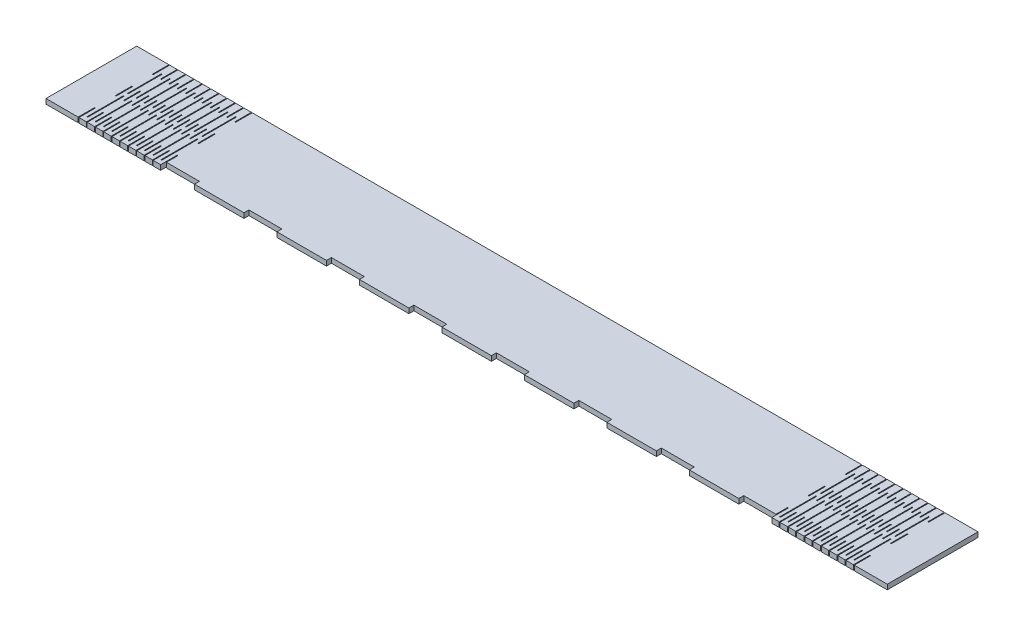
SolidWorks part; units mm, degrees
material "Beech"
ref_plane "Front Plane" through (0, 0, 0) normal (0, 0, 1) x (1, 0, 0)
ref_plane "Top Plane" through (0, 0, 0) normal (0, 1, 0) x (1, 0, 0)
ref_plane "Right Plane" through (0, 0, 0) normal (1, 0, 0) x (0, 0, -1)
sketch "Sketch1" plane through (0, 0, 0) normal (0, 1, 0) x (1, 0, 0)
  line L0 (-185, 27.5) -> (-185, -27.5)
  line L1 (-255, -27.5) -> (255, -27.5)
  line L2 (-255, -27.5) -> (-255, 27.5)
  line L3 (-255, 27.5) -> (255, 27.5)
  line L4 (255, -27.5) -> (255, 27.5)
  line L5 (-255, -27.5) -> (255, 27.5) construction
  line L6 (-255, 27.5) -> (255, -27.5) construction
  line L7 (185, 27.5) -> (185, -27.5)
  point P0 (0, 0)
  point P6 (-185, 27.5)
  point P7 (185, 27.5)
  point P10 (235, 27.5)
  point P13 (-235, 27.5)
  dimension "D1" = 510
  dimension "D2" = 70
  dimension "D3" = 70
  dimension "D4" = 50
  dimension "D5" = 50
  dimension "D6" = 55
  dimension "D7" = 370
extrude "Boss-Extrude1" add sketch "Sketch1" along normal blind 3 contours L3 L2 L1 L0 | L7 L3 L0 L1 | L3 L7 L1 L4 region at (0, 0, 0) region at (-220, 0, 0) region at (220, 0, 0)
sketch "Sketch2" plane through (0, 3, 0) normal (0, 1, 0) x (1, 0, 0)
  line L0 (-255, 27.5) -> (255, 27.5) construction
  line L2 (-235, 27.5) -> (-235, -27.5)
  line L3 (-255, -27.5) -> (255, -27.5) construction
  line L4 (-185, 27.5) -> (-185, -27.5)
  line L5 (185, 27.5) -> (185, -27.5)
  line L6 (235, 27.5) -> (235, -27.5)
  line L7 (-135, -27.5) -> (-115, -27.5)
  line L8 (-185, -27.5) -> (-165, -27.5)
  line L9 (-185, -27.5) -> (-185, -24.5)
  line L10 (-185, -24.5) -> (-165, -24.5)
  line L11 (-165, -27.5) -> (-165, -24.5)
  line L12 (-135, -24.5) -> (-115, -24.5)
  line L13 (-115, -27.5) -> (-115, -24.5)
  line L14 (-85, -27.5) -> (-65, -27.5)
  line L15 (-85, -24.5) -> (-65, -24.5)
  line L16 (-65, -27.5) -> (-65, -24.5)
  line L17 (-35, -27.5) -> (-15, -27.5)
  line L18 (-35, -24.5) -> (-15, -24.5)
  line L19 (-15, -27.5) -> (-15, -24.5)
  line L20 (15, -27.5) -> (35, -27.5)
  line L21 (15, -24.5) -> (35, -24.5)
  line L22 (35, -27.5) -> (35, -24.5)
  line L23 (65, -27.5) -> (85, -27.5)
  line L24 (65, -24.5) -> (85, -24.5)
  line L25 (85, -27.5) -> (85, -24.5)
  line L26 (115, -27.5) -> (135, -27.5)
  line L27 (115, -24.5) -> (135, -24.5)
  line L28 (135, -27.5) -> (135, -24.5)
  line L29 (165, -27.5) -> (185, -27.5)
  line L30 (165, -24.5) -> (185, -24.5)
  line L31 (185, -27.5) -> (185, -24.5)
  line L32 (165, -24.5) -> (165, -27.5)
  line L33 (115, -24.5) -> (115, -27.5)
  line L34 (65, -27.5) -> (65, -24.5)
  line L35 (15, -24.5) -> (15, -27.5)
  line L36 (-35, -24.5) -> (-35, -27.5)
  line L37 (-85, -27.5) -> (-85, -24.5)
  line L38 (-135, -24.5) -> (-135, -27.5)
  line L39 (-185, -24.5) -> (-185, -27.5)
  point P0 (-235, 27.5)
  point P1 (-185, 27.5)
  point P4 (185, 27.5)
  point P5 (235, 27.5)
  line M6 (-255, -27.5) -> (255, -27.5)
  dimension "D1" = 370
  dimension "D2" = 50
  dimension "D3" = 50
  dimension "D4" = 20
  dimension "D5" = 20
  dimension "D6" = 3
  dimension "D7" = 30
extrude "Cut-Extrude1" cut sketch "Sketch2" against normal through all contours L11 L10 L4 M6 | L12 L38 L13 M6 | L37 L16 L15 M6 | L18 L36 L19 M6 | L21 L35 L22 M6 | L27 L33 L28 M6 | L30 L32 L5 M6 | L24 L25 L23 L34 region at (-175, 3, 26) region at (175, 3, 26) region at (125, 3, 26) region at (25, 3, 26) region at (-25, 3, 26) region at (-75, 3, 26) region at (-125, 3, 26)
sketch "Sketch3" plane through (0, 3, 0) normal (0, 1, 0) x (1, 0, 0)
  line L0 (-255, 27.5) -> (255, 27.5) construction
  line L1 (185, 27.5) -> (185, -27.5) construction
  line L2 (185, -27.5) -> (235, 27.5) construction
  line L3 (235, 27.5) -> (235, -27.5) construction
  line L4 (185, -27.5) -> (255, -27.5) construction
  line L5 (185, 27.5) -> (185, 17.5)
  line L6 (190, 27.5) -> (190, 17.5)
  line L7 (195, 27.5) -> (195, 17.5)
  line L8 (200, 27.5) -> (200, 17.5)
  line L9 (205, 27.5) -> (205, 17.5)
  line L10 (210, 27.5) -> (210, 17.5)
  line L11 (215, 27.5) -> (215, 17.5)
  line L12 (220, 27.5) -> (220, 17.5)
  line L13 (225, 27.5) -> (225, 17.5)
  line L14 (230, 27.5) -> (230, 17.5)
  line L15 (235, 27.5) -> (235, 17.5)
  line L16 (185, 5) -> (185, -5)
  line L17 (185, -17.5) -> (185, -27.5)
  line L18 (190, 5) -> (190, -5)
  line L19 (190, -17.5) -> (190, -27.5)
  line L20 (195, 5) -> (195, -5)
  line L21 (195, -17.5) -> (195, -27.5)
  line L22 (200, 5) -> (200, -5)
  line L23 (200, -17.5) -> (200, -27.5)
  line L24 (205, 5) -> (205, -5)
  line L25 (205, -17.5) -> (205, -27.5)
  line L26 (210, 5) -> (210, -5)
  line L27 (210, -17.5) -> (210, -27.5)
  line L28 (215, 5) -> (215, -5)
  line L29 (215, -17.5) -> (215, -27.5)
  line L30 (220, 5) -> (220, -5)
  line L31 (220, -17.5) -> (220, -27.5)
  line L32 (225, 5) -> (225, -5)
  line L33 (225, -17.5) -> (225, -27.5)
  line L34 (230, 5) -> (230, -5)
  line L35 (230, -17.5) -> (230, -27.5)
  line L36 (235, 5) -> (235, -5)
  line L37 (235, -17.5) -> (235, -27.5)
  line L38 (187.5, 20.5) -> (187.5, 0)
  line L39 (187.5, -2.75) -> (187.5, -24.75)
  line L40 (192.5, 20.5) -> (192.5, 0)
  line L41 (192.5, -2.75) -> (192.5, -24.75)
  line L42 (197.5, 20.5) -> (197.5, 0)
  line L43 (197.5, -2.75) -> (197.5, -24.75)
  line L44 (202.5, 20.5) -> (202.5, 0)
  line L45 (202.5, -2.75) -> (202.5, -24.75)
  line L46 (207.5, 20.5) -> (207.5, 0)
  line L47 (207.5, -2.75) -> (207.5, -24.75)
  line L48 (212.5, 20.5) -> (212.5, 0)
  line L49 (212.5, -2.75) -> (212.5, -24.75)
  line L50 (217.5, 20.5) -> (217.5, 0)
  line L51 (217.5, -2.75) -> (217.5, -24.75)
  line L52 (222.5, 20.5) -> (222.5, 0)
  line L53 (222.5, -2.75) -> (222.5, -24.75)
  line L54 (227.5, 20.5) -> (227.5, 0)
  line L55 (227.5, -2.75) -> (227.5, -24.75)
  line L56 (232.5, 20.5) -> (232.5, 0)
  line L57 (232.5, -2.75) -> (232.5, -24.75)
  line L58 (0, 27.5) -> (0, -27.5) construction
  line L59 (-15, -27.5) -> (15, -27.5) construction
  line L60 (-235, 27.5) -> (-235, -27.5) construction
  line L61 (-185, -27.5) -> (-235, 27.5) construction
  line L62 (-185, 27.5) -> (-185, -27.5) construction
  line L63 (-232.5, -2.75) -> (-232.5, -24.75)
  line L64 (-232.5, 20.5) -> (-232.5, 0)
  line L65 (-227.5, -2.75) -> (-227.5, -24.75)
  line L66 (-227.5, 20.5) -> (-227.5, 0)
  line L67 (-222.5, -2.75) -> (-222.5, -24.75)
  line L68 (-222.5, 20.5) -> (-222.5, 0)
  line L69 (-217.5, -2.75) -> (-217.5, -24.75)
  line L70 (-217.5, 20.5) -> (-217.5, 0)
  line L71 (-212.5, -2.75) -> (-212.5, -24.75)
  line L72 (-212.5, 20.5) -> (-212.5, 0)
  line L73 (-207.5, -2.75) -> (-207.5, -24.75)
  line L74 (-207.5, 20.5) -> (-207.5, 0)
  line L75 (-202.5, -2.75) -> (-202.5, -24.75)
  line L76 (-202.5, 20.5) -> (-202.5, 0)
  line L77 (-197.5, -2.75) -> (-197.5, -24.75)
  line L78 (-197.5, 20.5) -> (-197.5, 0)
  line L79 (-192.5, -2.75) -> (-192.5, -24.75)
  line L80 (-192.5, 20.5) -> (-192.5, 0)
  line L81 (-187.5, -2.75) -> (-187.5, -24.75)
  line L82 (-187.5, 20.5) -> (-187.5, 0)
  line L83 (-235, -17.5) -> (-235, -27.5)
  line L84 (-235, 5) -> (-235, -5)
  line L85 (-230, -17.5) -> (-230, -27.5)
  line L86 (-230, 5) -> (-230, -5)
  line L87 (-225, -17.5) -> (-225, -27.5)
  line L88 (-225, 5) -> (-225, -5)
  line L89 (-220, -17.5) -> (-220, -27.5)
  line L90 (-220, 5) -> (-220, -5)
  line L91 (-215, -17.5) -> (-215, -27.5)
  line L92 (-215, 5) -> (-215, -5)
  line L93 (-210, -17.5) -> (-210, -27.5)
  line L94 (-210, 5) -> (-210, -5)
  line L95 (-205, -17.5) -> (-205, -27.5)
  line L96 (-205, 5) -> (-205, -5)
  line L97 (-200, -17.5) -> (-200, -27.5)
  line L98 (-200, 5) -> (-200, -5)
  line L99 (-195, -17.5) -> (-195, -27.5)
  line L100 (-195, 5) -> (-195, -5)
  line L101 (-190, -17.5) -> (-190, -27.5)
  line L102 (-190, 5) -> (-190, -5)
  line L103 (-185, -17.5) -> (-185, -27.5)
  line L104 (-185, 5) -> (-185, -5)
  line L105 (-235, 27.5) -> (-235, 17.5)
  line L106 (-230, 27.5) -> (-230, 17.5)
  line L107 (-225, 27.5) -> (-225, 17.5)
  line L108 (-220, 27.5) -> (-220, 17.5)
  line L109 (-215, 27.5) -> (-215, 17.5)
  line L110 (-210, 27.5) -> (-210, 17.5)
  line L111 (-205, 27.5) -> (-205, 17.5)
  line L112 (-200, 27.5) -> (-200, 17.5)
  line L113 (-195, 27.5) -> (-195, 17.5)
  line L114 (-190, 27.5) -> (-190, 17.5)
  line L115 (-185, 27.5) -> (-185, 17.5)
  point P0 (185, 27.5)
  point P1 (235, 27.5)
  point P10 (0, 0)
  point P79 (0, 0)
  dimension "D1" = 20
  dimension "D2" = 50
  dimension "D3" = 11
  dimension "D4" = 0
  dimension "D5" = 10
  dimension "D6" = 10
  dimension "D7" = 12.5
  dimension "D8" = 10
  dimension "D9" = 12.5
  dimension "D10" = 11
  dimension "D11" = 20.5
  dimension "D12" = 10
  dimension "D13" = 22
extrude "Cut-Extrude-Thin2" cut sketch "Sketch3" against normal blind 10 thin thin type one direction wall 0.5
